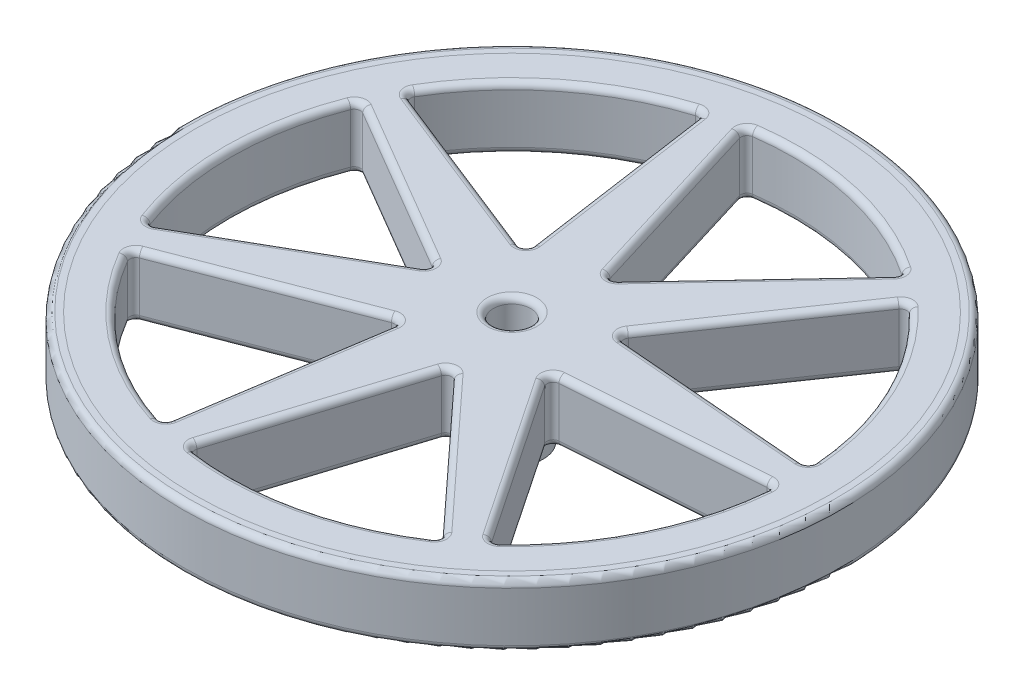
SolidWorks part; units mm, degrees
ref_plane "Front Plane" through (0, 0, 0) normal (0, 0, 1) x (1, 0, 0)
ref_plane "Top Plane" through (0, 0, 0) normal (0, 1, 0) x (1, 0, 0)
ref_plane "Right Plane" through (0, 0, 0) normal (1, 0, 0) x (0, 0, -1)
sketch "Sketch1" plane through (0, 0, 0) normal (0, 1, 0) x (1, 0, 0)
  circle A0 centre (0, 0) radius 52
  circle A1 centre (0, 0) radius 53
  circle A2 centre (0, 0) radius 5
  circle A3 centre (0, 0) radius 3
  dimension "D1" = 106
  dimension "D2" = 104
  dimension "D3" = 6
  dimension "D4" = 10
extrude "Boss-Extrude1" add sketch "Sketch1" along normal blind 10 contours A1 | A0
extrude "Boss-Extrude2" add sketch "Sketch1<3>" along normal blind 10 contours A0 A2 | A2 A3 | A3 region at (-50.5292, 0, 0) region at (-4.8586, 0, 0) region at (0, 0, 0)
sketch "Sketch1<3>" plane through (0, 0, 0) normal (0, 1, 0) x (1, 0, 0) same geometry as "Sketch1"
extrude "Boss-Extrude3" add sketch "Sketch1<4>" against normal blind 8 contours A2 A3 region at (-4.8586, 0, 0)
sketch "Sketch1<4>" plane through (0, 0, 0) normal (0, 1, 0) x (1, 0, 0) same geometry as "Sketch1"
sketch "Sketch4" plane through (0, 0, 0) normal (0, -1, 0) x (1, 0, 0)
  line L0 (-12.2104, 0) -> (-41.8763, 16.9958)
  line L1 (-12.2104, 0) -> (-41.7451, -17.3157)
  arc A0 (-41.8763, 16.9958) -> (-41.7451, -17.3157) centre (0, 0) ccw
extrude "Cut-Extrude1" cut sketch "Sketch4" against normal through all
pattern_circular "CirPattern1" count 7 over 360 about axis through (0, 0, 0) along (0, 1, 0) of "Cut-Extrude1"
extrude "Cut-Extrude2" cut sketch "Sketch1<5>" against normal through all both and the other way through all contours A3 region at (0, 0, 0)
sketch "Sketch1<5>" plane through (0, 0, 0) normal (0, 1, 0) x (1, 0, 0) same geometry as "Sketch1"
fillet "Fillet2" radius 1 67 edges at (-27.0434, 10, 8.4979) (0, 10, 53) (0, 0, 53) (0, 0, 5) (-41.7451, 5, -17.3157) (-41.8763, 5, 16.9958) (-12.2104, 5, 0) (-45.1935, 10, -0.1728) (-26.9777, 10, -8.6578) (-45.1935, 0, -0.1728) (-27.0434, 0, 8.4979) (-26.9777, 0, -8.6578) (-39.5655, 5, 21.8415) (-12.8215, 5, 43.3369) (-7.6131, 5, 9.5465) (-28.3128, 10, 35.2259) (-10.2173, 10, 26.4417) (-23.5893, 10, 15.694) (-28.3128, 0, 35.2259) (-10.2173, 0, 26.4417) (-23.5893, 0, 15.694) (-7.5924, 5, 44.5515) (25.8881, 5, 37.0444) (2.7171, 5, 11.9043) (9.888, 10, 44.0989) (14.3026, 10, 24.4744) (-2.4376, 10, 28.2279) (9.888, 0, 44.0989) (14.3026, 0, 24.4744) (-2.4376, 0, 28.2279) (30.098, 5, 33.7134) (45.1034, 5, 2.8567) (11.0012, 5, 5.2979) (40.6429, 10, 19.7644) (28.0523, 10, 4.0773) (20.5496, 10, 19.5056) (40.6429, 0, 19.7644) (28.0523, 0, 4.0773) (20.5496, 0, 19.5056) (45.124, 5, -2.5116) (30.355, 5, -33.4822) (11.0012, 5, -5.2979) (40.7929, 10, -19.453) (20.6781, 10, -19.39) (28.0626, 10, -3.9048) (40.7929, 0, -19.453) (20.6781, 0, -19.39) (28.0626, 0, -3.9048) (26.1707, 5, -36.8453) (-7.2514, 5, -44.6083) (2.7171, 5, -11.9043) (10.225, 10, -44.0219) (-2.2671, 10, -28.2563) (14.4439, 10, -24.3748) (10.225, 0, -44.0219) (-2.2671, 0, -28.2563) (14.4439, 0, -24.3748) (-12.4897, 5, -43.4337) (-39.3973, 5, -22.1435) (-7.6131, 5, -9.5465) (-28.0425, 10, -35.4415) (-23.5052, 10, -15.845) (-10.0514, 10, -26.4901) (-28.0425, 0, -35.4415) (-23.5052, 0, -15.845) (-10.0514, 0, -26.4901) (0, 10, 3)
sketch "Sketch5" plane through (0, 10, 0) normal (0, 1, 0) x (1, 0, 0)
  circle A0 centre (0, 0) radius 51
  dimension "D1" = 102
split line "Split Line1"
